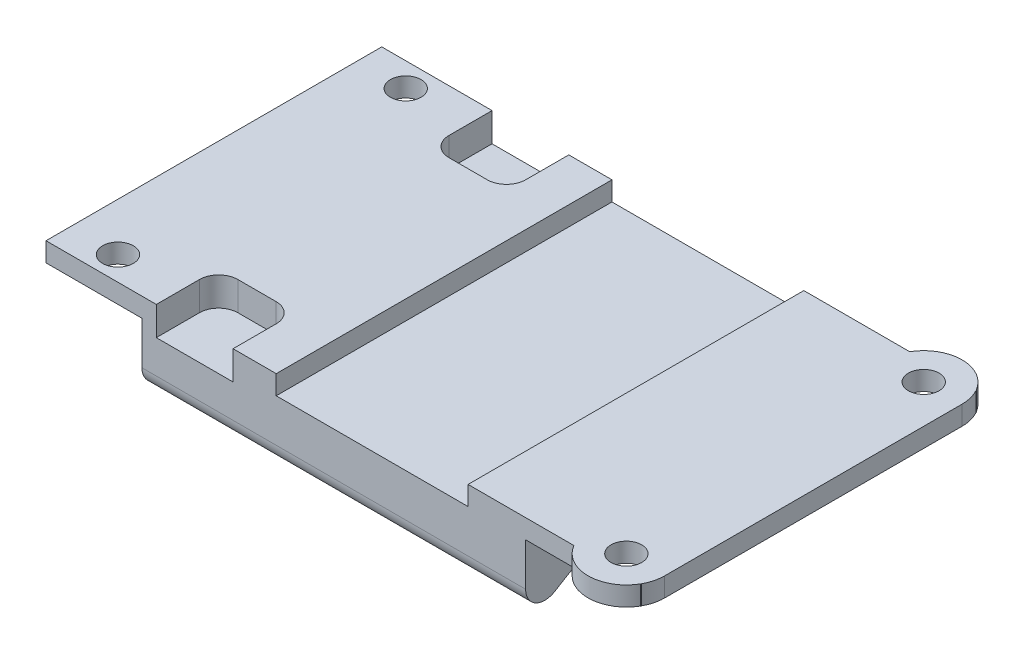
SolidWorks part; units mm, degrees
material "PEI"
ref_plane "Front Plane" through (0, 0, 0) normal (0, 0, 1) x (1, 0, 0)
ref_plane "Top Plane" through (0, 0, 0) normal (0, 1, 0) x (1, 0, 0)
ref_plane "Right Plane" through (0, 0, 0) normal (1, 0, 0) x (0, 0, -1)
sketch "Sketch1" plane through (0, 0, 0) normal (0, 1, 0) x (1, 0, 0)
  line L1 (20, -17.5) -> (-20, -17.5)
  line L2 (20, -17.5) -> (20, 17.5)
  line L3 (20, 17.5) -> (-20, 17.5)
  line L4 (-20, -17.5) -> (-20, 17.5)
  line L5 (20, -17.5) -> (-20, 17.5) construction
  line L6 (20, 17.5) -> (-20, -17.5) construction
  point P0 (0, 0)
  dimension "D1" = 35
  dimension "D2" = 40
extrude "Boss-Extrude1" add sketch "Sketch1" against normal blind 10
sketch "Sketch2" plane through (20, 0, 0) normal (1, 0, 0) x (0, 0, -1)
  line L0 (-17.5, -10) -> (-12.5, -7)
  line L1 (-12.5, -7) -> (12.5, -7)
  line L2 (0, -7) -> (0, -10)
  line L3 (17.5, -10) -> (12.5, -7)
  line L4 (17.5, 0) -> (-17.5, 0)
  line L5 (-17.5, 0) -> (-17.5, -10)
  line L6 (-17.5, -10) -> (17.5, -10)
  line L7 (17.5, -10) -> (17.5, 0)
  line L8 (17.5, 0) -> (-17.5, 0)
  line L9 (-17.5, 0) -> (-17.5, -10)
  line L10 (-17.5, -10) -> (17.5, -10)
  line L11 (17.5, -10) -> (17.5, 0)
  line M7 (-17.5, -10) -> (17.5, -10)
  dimension "D2" = 5
  dimension "D3" = 3
  dimension "D1" = 0
extrude "Cut-Extrude1" cut sketch "Sketch2" against normal through all and the other way through all contours L2 L1 L0 M7 | L3 L1 L2 M7 region at (20, -8.5833, 7.5694) region at (20, -8.5833, -7.5694)
fillet "Fillet1" radius 2 4 edges at (0, -7, 12.5) (0, -7, -12.5) (0, -10, -17.5) (0, -10, 17.5)
sketch "Sketch4" plane through (-20, 0, 0) normal (-1, 0, 0) x (0, 0, 1)
  line L1 (-17.5, 0) -> (17.5, 0)
  line L2 (-17.5, 0) -> (-17.5, -2)
  line L3 (-17.5, -2) -> (17.5, -2)
  line L4 (17.5, 0) -> (17.5, -2)
  line L6 (-17.5, 0) -> (-17.5, -6.4676)
  line L7 (-14.471, -8.1826) -> (-12.975, -7.285)
  line L11 (17.5, 0) -> (-17.5, 0)
  line L12 (-17.5, 0) -> (-17.5, -6.4676)
  line L13 (-14.471, -8.1826) -> (-12.975, -7.285)
  line L17 (17.5, 0) -> (-17.5, 0)
  line L19 (-11.946, -7) -> (11.946, -7)
  line L20 (-11.946, -7) -> (11.946, -7)
  line L21 (12.975, -7.285) -> (14.471, -8.1826)
  line L22 (12.975, -7.285) -> (14.471, -8.1826)
  line L23 (17.5, -6.4676) -> (17.5, 0)
  line L24 (17.5, -6.4676) -> (17.5, 0)
  arc A4 (-17.5, -6.4676) -> (-14.471, -8.1826) centre (-15.5, -6.4676) ccw
  arc A5 (-17.5, -6.4676) -> (-14.471, -8.1826) centre (-15.5, -6.4676) ccw
  arc A6 (-11.946, -7) -> (-12.975, -7.285) centre (-11.946, -9) ccw
  arc A7 (-11.946, -7) -> (-12.975, -7.285) centre (-11.946, -9) ccw
  arc A12 (12.975, -7.285) -> (11.946, -7) centre (11.946, -9) ccw
  arc A13 (12.975, -7.285) -> (11.946, -7) centre (11.946, -9) ccw
  arc A14 (14.471, -8.1826) -> (17.5, -6.4676) centre (15.5, -6.4676) ccw
  arc A15 (14.471, -8.1826) -> (17.5, -6.4676) centre (15.5, -6.4676) ccw
  line M12 (-17.5, 0) -> (-17.5, -6.4676)
  line M20 (17.5, -6.4676) -> (17.5, 0)
  line M21 (17.5, 0) -> (-17.5, 0)
  dimension "D2" = 2
  dimension "D1" = 0
extrude "Boss-Extrude2" add sketch "Sketch4" along normal blind 10 contours L3 M12 M20 M21 region at (-20, -1, 0)
sketch "Sketch5" plane through (20, 0, 0) normal (1, 0, 0) x (0, 0, -1)
  line L1 (-17.5, 0) -> (17.5, 0)
  line L2 (-17.5, 0) -> (-17.5, -2)
  line L3 (-17.5, -2) -> (17.5, -2)
  line L4 (17.5, 0) -> (17.5, -2)
  line L6 (12.975, -7.285) -> (14.471, -8.1826)
  line L7 (17.5, -6.4676) -> (17.5, 0)
  line L8 (17.5, 0) -> (-17.5, 0)
  line L12 (12.975, -7.285) -> (14.471, -8.1826)
  line L13 (17.5, -6.4676) -> (17.5, 0)
  line L14 (17.5, 0) -> (-17.5, 0)
  line L19 (-17.5, 0) -> (-17.5, -6.4676)
  line L20 (-17.5, 0) -> (-17.5, -6.4676)
  line L21 (-14.471, -8.1826) -> (-12.975, -7.285)
  line L22 (-14.471, -8.1826) -> (-12.975, -7.285)
  line L23 (-11.946, -7) -> (11.946, -7)
  line L24 (-11.946, -7) -> (11.946, -7)
  arc A4 (14.471, -8.1826) -> (17.5, -6.4676) centre (15.5, -6.4676) ccw
  arc A5 (14.471, -8.1826) -> (17.5, -6.4676) centre (15.5, -6.4676) ccw
  arc A6 (-17.5, -6.4676) -> (-14.471, -8.1826) centre (-15.5, -6.4676) ccw
  arc A7 (-17.5, -6.4676) -> (-14.471, -8.1826) centre (-15.5, -6.4676) ccw
  arc A12 (-11.946, -7) -> (-12.975, -7.285) centre (-11.946, -9) ccw
  arc A13 (-11.946, -7) -> (-12.975, -7.285) centre (-11.946, -9) ccw
  arc A14 (12.975, -7.285) -> (11.946, -7) centre (11.946, -9) ccw
  arc A15 (12.975, -7.285) -> (11.946, -7) centre (11.946, -9) ccw
  line M14 (17.5, -6.4676) -> (17.5, 0)
  line M15 (17.5, 0) -> (-17.5, 0)
  line M16 (-17.5, 0) -> (-17.5, -6.4676)
  dimension "D2" = 2
  dimension "D1" = 0
extrude "Boss-Extrude3" add sketch "Sketch5" along normal blind 12 contours L3 M16 M14 M15 region at (20, -1, 0)
sketch "Sketch6" plane through (0, -2, 0) normal (0, -1, 0) x (1, 0, 0)
  line L0 (0, 0) -> (-25, 0)
  line L1 (-25, 0) -> (-25, 15)
  line L4 (-20, -17.5) -> (-20, 17.5)
  line L5 (-20, 17.5) -> (-30, 17.5)
  line L6 (-30, 17.5) -> (-30, -17.5)
  line L7 (-30, -17.5) -> (-20, -17.5)
  line L8 (-20, -17.5) -> (-20, 17.5)
  line L10 (-30, 17.5) -> (-30, -17.5)
  line L11 (-30, -17.5) -> (-20, -17.5)
  line L12 (20, -11.946) -> (20, 11.946)
  line L13 (20, 11.946) -> (-20, 11.946)
  line L14 (-20, 11.946) -> (-20, -11.946)
  line L15 (-20, -11.946) -> (20, -11.946)
  line L16 (20, -11.946) -> (20, 11.946)
  line L17 (20, 11.946) -> (-20, 11.946)
  line L18 (-20, 11.946) -> (-20, -11.946)
  line L19 (-20, -11.946) -> (20, -11.946)
  line L23 (-20, 17.5) -> (-30, 17.5)
  circle A0 centre (-25, 15) radius 1.6
  circle A1 centre (-25, -15) radius 1.6
  dimension "D5" = 3.2
  dimension "D3" = 15
  dimension "D4" = 25
  dimension "D1" = 0
  dimension "D2" = 0
extrude "Cut-Extrude2" cut sketch "Sketch6" against normal blind 10 contours A1 | A0 region at (-26.0994, -2, 16.0994) region at (-25, -2, -15)
sketch "Sketch7" plane through (0, 0, 0) normal (0, 1, 0) x (1, 0, 0)
  line L0 (-25, -15) -> (-14.5, -15)
  line L1 (-14.5, -15) -> (-14.5, -14.5)
  line L2 (0, 0) -> (-16.7205, 0)
  line L3 (-10.5, -19) -> (-18.5, -19)
  line L4 (32, 17.5) -> (-30, 17.5)
  line L5 (-30, 17.5) -> (-30, -17.5)
  line L6 (-30, -17.5) -> (32, -17.5)
  line L7 (32, -17.5) -> (32, 17.5)
  line L8 (32, 17.5) -> (-30, 17.5)
  line L9 (-30, 17.5) -> (-30, -17.5)
  line L11 (32, -17.5) -> (32, 17.5)
  line L12 (-10.5, -19) -> (-10.5, -11)
  line L13 (-10.5, -11) -> (-18.5, -11)
  line L14 (-18.5, -19) -> (-18.5, -11)
  line L15 (-10.5, -19) -> (-18.5, -11) construction
  line L16 (-10.5, -11) -> (-18.5, -19) construction
  line L17 (-10.5, 19) -> (-18.5, 19)
  line L18 (-18.5, 19) -> (-18.5, 11)
  line L19 (-10.5, 19) -> (-10.5, 11)
  line L20 (-10.5, 11) -> (-18.5, 11)
  line L26 (-30, -17.5) -> (32, -17.5)
  dimension "D4" = 8
  dimension "D2" = 0.5
  dimension "D3" = 10.5
  dimension "D5" = 8
  dimension "D1" = 0
extrude "Cut-Extrude3" cut sketch "Sketch7" against normal blind 3 contours L20 L19 L8 L18 | L12 L13 L14 L3 region at (-14.5, 0, -14.25)
sketch "Sketch8" plane through (0, 0, 17.5) normal (0, 0, 1) x (1, 0, 0)
  line L0 (-10.5, 0) -> (32, 0) construction
  line L1 (14, 2) -> (-6, 2)
  line L2 (14, 2) -> (14, -2)
  line L3 (14, -2) -> (-6, -2)
  line L4 (-6, 2) -> (-6, -2)
  line L5 (14, 2) -> (-6, -2) construction
  line L6 (14, -2) -> (-6, 2) construction
  line L12 (-10.5, -3) -> (-18.5, -3)
  line L13 (-18.5, -3) -> (-18.5, 0)
  line L14 (-18.5, 0) -> (-30, 0)
  line L15 (-30, 0) -> (-30, -2)
  line L16 (-30, -2) -> (-20, -2)
  line L17 (-20, -2) -> (-20, -6.4676)
  line L18 (-20, -6.4676) -> (20, -6.4676)
  line L19 (20, -6.4676) -> (20, -2)
  line L20 (20, -2) -> (32, -2)
  line L21 (32, -2) -> (32, 0)
  line L22 (32, 0) -> (-10.5, 0)
  line L23 (-10.5, 0) -> (-10.5, -3)
  line L24 (-10.5, -3) -> (-18.5, -3)
  line L25 (-18.5, -3) -> (-18.5, 0)
  line L26 (-18.5, 0) -> (-30, 0)
  line L27 (-30, 0) -> (-30, -2)
  line L28 (-30, -2) -> (-20, -2)
  line L29 (-20, -2) -> (-20, -6.4676)
  line L30 (-20, -6.4676) -> (20, -6.4676)
  line L31 (20, -6.4676) -> (20, -2)
  line L32 (20, -2) -> (32, -2)
  line L33 (32, -2) -> (32, 0)
  line L34 (32, 0) -> (-10.5, 0)
  line L35 (-10.5, 0) -> (-10.5, -3)
  point P2 (4, 0)
  point P23 (-20, -4.2338)
  line M25 (32, 0) -> (-10.5, 0)
  dimension "D2" = 2
  dimension "D3" = 20
  dimension "D4" = 24
  dimension "D1" = 0
extrude "Cut-Extrude5" cut sketch "Sketch8" against normal through all contours L4 L3 L2 M25 region at (4, -1, 17.5)
fillet "Fillet2" radius 2 4 edges at (-18.5, -1.5, 11) (-10.5, -1.5, 11) (-18.5, -1.5, -11) (-10.5, -1.5, -11)
sketch "Sketch10" plane through (0, -2, 0) normal (0, -1, 0) x (1, 0, 0)
  line L0 (-25, 15) -> (28.5, 15)
  line L1 (0, 0) -> (0, 15.5)
  line L2 (0, 15.5) -> (28.5, 15.5)
  line L3 (28.5, 15.5) -> (28.5, 15)
  line L4 (20, 17.5) -> (20, -17.5)
  line L5 (20, -17.5) -> (32, -17.5)
  line L6 (32, -17.5) -> (32, 17.5)
  line L7 (32, 17.5) -> (20, 17.5)
  line L8 (20, 17.5) -> (20, -17.5)
  line L9 (20, -17.5) -> (32, -17.5)
  line L10 (32, -17.5) -> (32, 17.5)
  line L12 (-20, -17.5) -> (-20, 17.5)
  line L13 (-20, 17.5) -> (-30, 17.5)
  line L14 (-30, 17.5) -> (-30, -17.5)
  line L15 (-30, -17.5) -> (-20, -17.5)
  line L16 (-20, -17.5) -> (-20, 17.5)
  line L18 (-30, 17.5) -> (-30, -17.5)
  line L19 (-30, -17.5) -> (-20, -17.5)
  line L20 (0, 0) -> (12.4483, 0)
  line L21 (32.5, 15.5) -> (32.5, -15.5)
  line L27 (32, 17.5) -> (20, 17.5)
  line L28 (-20, 17.5) -> (-30, 17.5)
  circle A2 centre (28.5, 15.5) radius 1.6
  circle A3 centre (28.5, 15.5) radius 4
  circle A4 centre (28.5, -15.5) radius 1.6
  circle A5 centre (28.5, -15.5) radius 4
  line M13 (32, -17.5) -> (32, 17.5)
  dimension "D4" = 3.2
  dimension "D6" = 8
  dimension "D3" = 53.5
  dimension "D5" = 15.5
  dimension "D1" = 0
  dimension "D2" = 0
extrude "Cut-Extrude6" cut sketch "Sketch10" against normal through all contours A4 | A2 region at (28.5, -2, -15.5)
extrude "Boss-Extrude4" add sketch "Sketch10<4>" against normal blind 2 contours L27 A3 | L10 A3 | A5 L9 | A5 L10 | A5 L21 A3 M13 region at (32.2545, -2, 0) region at (32.2011, -2, 15.5) region at (28.5, -2, -18.3201) region at (28.5, -2, 18.3201) region at (32.2011, -2, -15.5)
sketch "Sketch10<4>" plane through (0, -2, 0) normal (0, -1, 0) x (1, 0, 0) same geometry as "Sketch10"
